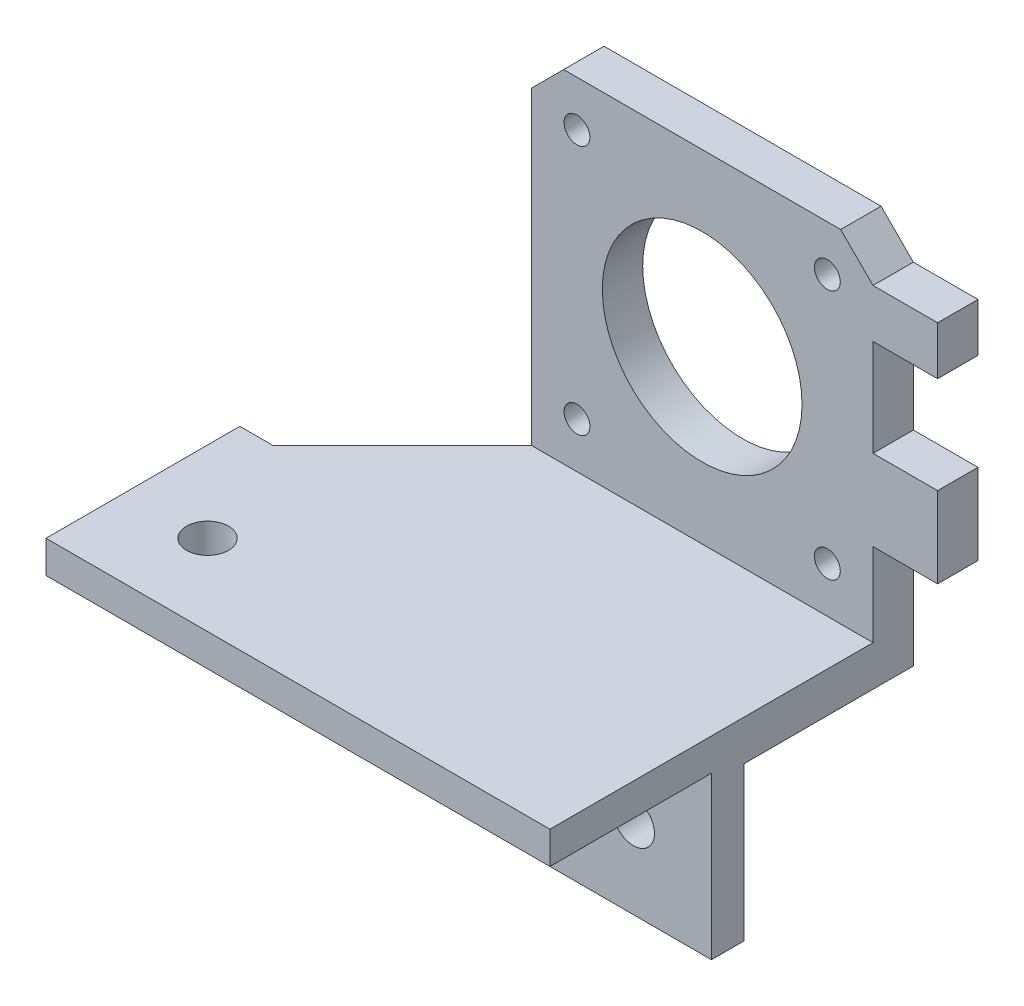
SolidWorks part; units mm, degrees
ref_plane "Přední rovina" through (0, 0, 0) normal (0, 0, 1) x (1, 0, 0)
ref_plane "Horní rovina" through (0, 0, 0) normal (0, 1, 0) x (1, 0, 0)
ref_plane "Pravá rovina" through (0, 0, 0) normal (1, 0, 0) x (0, 0, -1)
sketch "Skica1" plane through (0, 0, 0) normal (0, 0, 1) x (1, 0, 0)
  line L0 (-78.3, 11.0289) -> (-44, 11.0289) construction
  line L1 (-40, -12.9711) -> (-102.3916, -12.9711)
  line L2 (-40, -12.9711) -> (-40, 11.0289)
  line L3 (-40, 11.0289) -> (-102.3916, 11.0289)
  line L4 (-102.3916, -12.9711) -> (-102.3916, 11.0289)
extrude "Přidat vysunutím1" add sketch "Skica1" along normal blind 4
sketch "Skica2" plane through (0, 0, 4) normal (0, 0, 1) x (1, 0, 0)
  line L0 (-82.3, 49.3289) -> (-82.3, 15.0289) construction
  line L1 (-40, 11.0289) -> (-82.3, 11.0289)
  line L2 (-40, 11.0289) -> (-40, 6.0289)
  line L3 (-40, 6.0289) -> (-82.3, 6.0289)
  line L4 (-82.3, 11.0289) -> (-82.3, 6.0289)
  dimension "D1" = 5
extrude "Přidat vysunutím2" add sketch "Skica2" along normal up to surface (16 mm away)
sketch "Skica3" plane through (0, 0, 20) normal (0, 0, 1) x (1, 0, 0)
  line L0 (-82.3, 49.3289) -> (-82.3, 15.0289) construction
  line L1 (-40, 6.0289) -> (-82.3, 6.0289)
  line L2 (-40, 6.0289) -> (-40, 49.3289)
  line L3 (-44, 53.3289) -> (-78.3, 53.3289)
  line L4 (-82.3, 6.0289) -> (-82.3, 49.3289)
  line L5 (-44, 53.3289) -> (-78.3, 53.3289) construction
  line L6 (-40, 49.3289) -> (-44, 53.3289)
  line L7 (-78.3, 53.3289) -> (-82.3, 49.3289)
  circle A0 centre (-45.65, 47.6789) radius 1.6
  circle A1 centre (-76.65, 47.6789) radius 1.6
  circle A2 centre (-76.65, 16.6789) radius 1.6
  circle A3 centre (-45.65, 16.6789) radius 1.6
  circle A4 centre (-61.15, 32.1789) radius 12.3643
  dimension "D1" = 3.2
  dimension "D2" = 2
  dimension "D3" = 2
extrude "Přidat vysunutím5" add sketch "Skica3" along normal blind 5
chamfer "Zkosení1" distance 16 angle 45 1 edges at (-82.3, 8.5289, 4)
sketch "Skica4" plane through (0, 0, 4) normal (0, 0, 1) x (1, 0, 0)
  line L0 (-89.6556, -12.9711) -> (-89.6556, -2.9711) construction
  line L1 (-102.3916, -12.9711) -> (-40, -12.9711) construction
  circle A0 centre (-89.6556, -2.9711) radius 2.6
  circle A1 centre (-69.6556, -2.9711) radius 2.6
  circle A2 centre (-49.6556, -2.9711) radius 2.6
  dimension "D2" = 5.2
  dimension "D1" = 10
  dimension "D3" = 3
extrude "Odebrat vysunutím1" cut sketch "Skica4" against normal blind 4
sketch "Skica5" plane through (0, 0, 0) normal (0, 0, -1) x (-1, 0, 0)
  line L0 (350, 7.0289) -> (0, 7.0289) construction
  line L1 (40, 11.0289) -> (102.3916, 11.0289)
  line L2 (40, 11.0289) -> (40, 7.0289)
  line L3 (40, 7.0289) -> (102.3916, 7.0289)
  line L4 (102.3916, 11.0289) -> (102.3916, 7.0289)
  line L6 (102.3916, 11.0289) -> (102.3916, -12.9711) construction
extrude "Přidat vysunutím6" add sketch "Skica5" along normal up to surface (20 mm away)
sketch "Skica6" plane through (0, 11.0289, 0) normal (0, 1, 0) x (1, 0, 0)
  line L0 (-40, 20) -> (-102.3916, 20) construction
  line L1 (-102.3916, -4) -> (-102.3916, 20) construction
  circle A0 centre (-92.3916, 10) radius 2.6
  dimension "D2" = 5.2
  dimension "D1" = 10
  dimension "D3" = 10
extrude "Odebrat vysunutím2" cut sketch "Skica6" against normal blind 4
mirror "Zrcadlit2" about plane through (-350, -6.1091, -20) normal (0, 0, 1) of bodies 108
sketch "Skica7" plane through (-102.3916, 0, 0) normal (-1, 0, 0) x (0, 0, 1)
  line L1 (-20, -18.6064) -> (32.5479, -18.6064)
  line L2 (-20, -18.6064) -> (-20, 54.7938)
  line L3 (-20, 54.7938) -> (32.5479, 54.7938)
  line L4 (32.5479, -18.6064) -> (32.5479, 54.7938)
extrude "Odebrat vysunutím3" cut sketch "Skica7" against normal blind 80
sketch "Skica8" plane through (-40, 0, 0) normal (1, 0, 0) x (0, 0, -1)
  line L0 (60, 11.0289) -> (60, 49.3289) construction
  line L1 (65, 49.3289) -> (60, 49.3289)
  line L2 (65, 49.3289) -> (65, 43.3289)
  line L3 (65, 43.3289) -> (60, 43.3289)
  line L4 (60, 49.3289) -> (60, 43.3289)
  line L5 (65, 6.0289) -> (65, 49.3289) construction
  line L6 (65, 21.3289) -> (60, 21.3289)
  line L7 (65, 21.3289) -> (65, 31.3289)
  line L8 (65, 31.3289) -> (60, 31.3289)
  line L9 (60, 21.3289) -> (60, 31.3289)
  line L10 (20, 43.3289) -> (400, 43.3289) construction
  line L11 (20, 31.3289) -> (400, 31.3289) construction
  dimension "D1" = 10
extrude "Přidat vysunutím7" add sketch "Skica8" along normal blind 8
